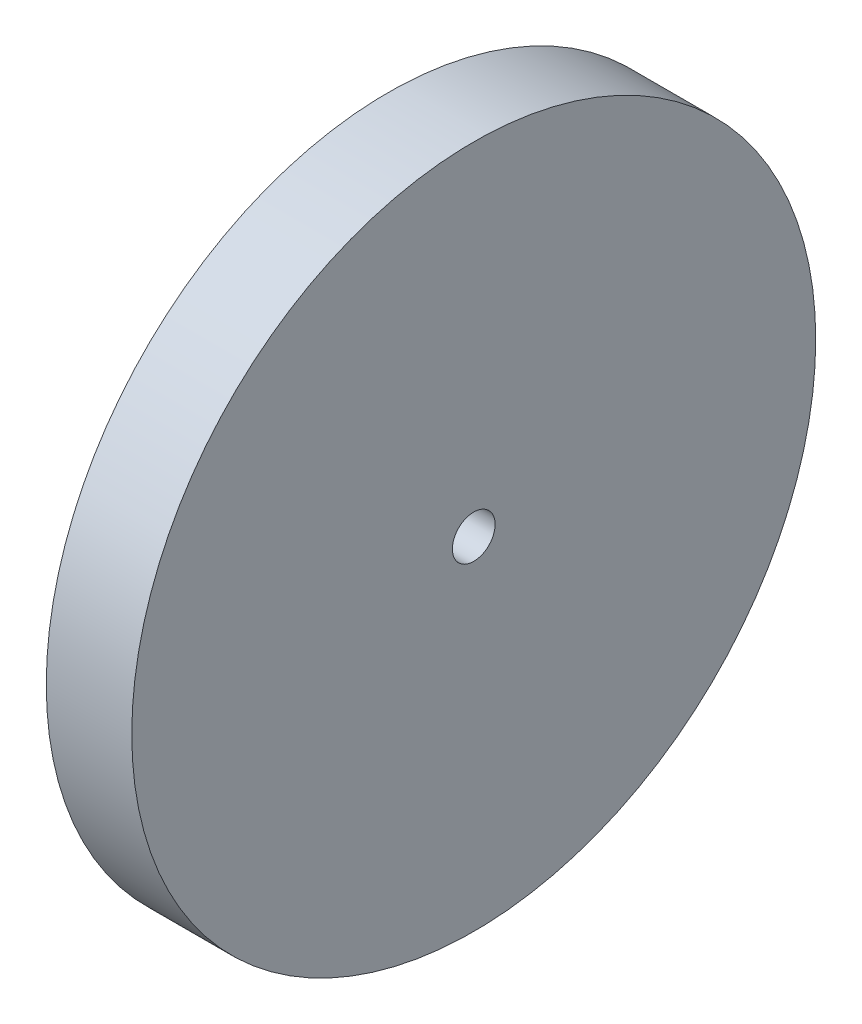
SolidWorks part; units mm, degrees
ref_plane "Front Plane" through (0, 0, 0) normal (0, 0, 1) x (1, 0, 0)
ref_plane "Top Plane" through (0, 0, 0) normal (0, 1, 0) x (1, 0, 0)
ref_plane "Right Plane" through (0, 0, 0) normal (1, 0, 0) x (0, 0, -1)
sketch "Sketch3" plane through (0, 0, 0) normal (0, 1, 0) x (1, 0, 0)
  line L0 (0, 0) -> (0, 38.1)
  line L1 (0, 38.1) -> (-9.525, 38.1)
  line L2 (-9.525, 38.1) -> (-9.525, 28.575)
  line L3 (-9.525, 28.575) -> (-3.3142, 28.575)
  line L4 (-3.3142, 28.575) -> (-3.3142, 15.875)
  line L5 (-3.3142, 15.875) -> (-9.6641, 9.525)
  line L6 (-9.6641, 9.525) -> (-9.6641, 0)
  line L7 (-9.6641, 0) -> (0, 0)
  dimension "D1" = 9.525
  dimension "D2" = 9.525
  dimension "D3" = 38.1
  dimension "D4" = 8.9802
  dimension "D5" = 9.525
  dimension "D6" = 12.7
ref_axis "Axis1" through (-9.6641, 0, 0) along (1, 0, 0)
revolve "Revolve1" add sketch "Sketch3" angle 360 about L7
sketch "Sketch5" plane through (-9.6642, 0, 0) normal (-1, 0, 0) x (0, 0, 1)
  circle A0 centre (0, 0) radius 2.3813
  dimension "D1" = 4.7625
extrude "Cut-Extrude2" cut sketch "Sketch5" against normal through all
